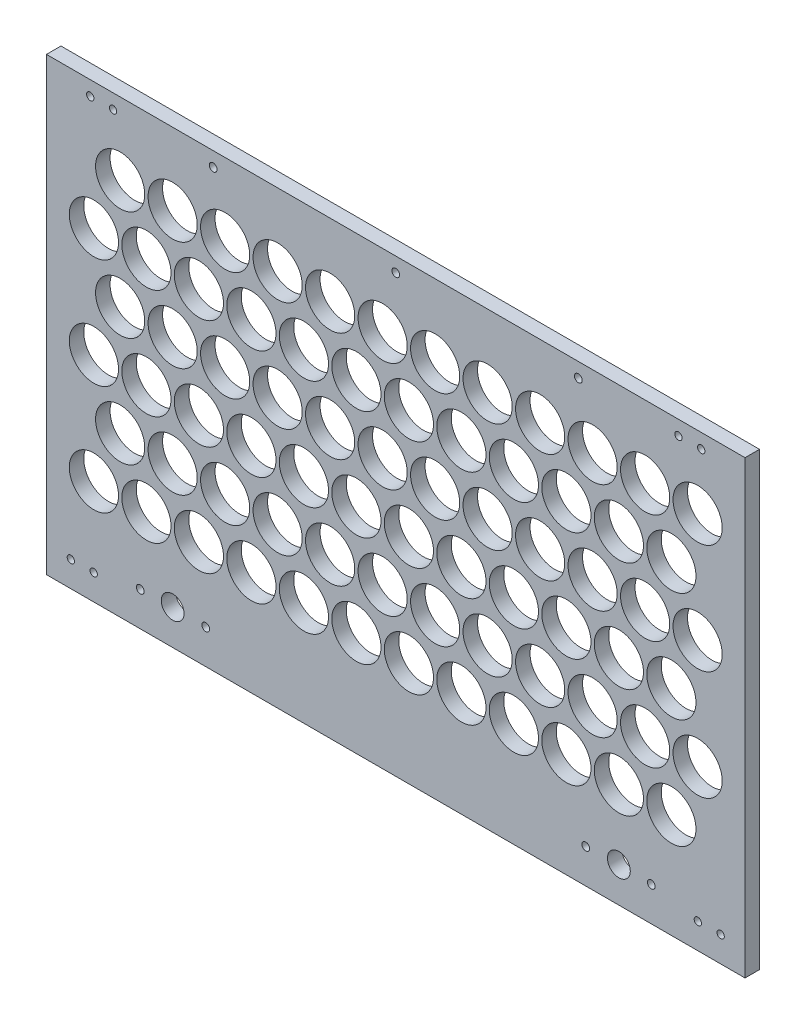
SolidWorks part; units mm, degrees
material "ABS"
ref_plane "X-Y Datum" through (0, 0, 0) normal (0, 0, 1) x (1, 0, 0)
ref_plane "X-Z Datum" through (0, 0, 0) normal (0, 1, 0) x (1, 0, 0)
ref_plane "Y-Z Datum" through (0, 0, 0) normal (1, 0, 0) x (0, 0, -1)
sketch "Sketch1" plane through (0, 0, 0) normal (0, 0, 1) x (1, 0, 0)
  line L1 (-143.025, 70.775) -> (143.025, 70.775)
  line L2 (-143.025, 70.775) -> (-143.025, -70.775)
  line L3 (-143.025, -70.775) -> (143.025, -70.775)
  line L4 (143.025, 70.775) -> (143.025, -70.775)
  line L5 (-143.025, 70.775) -> (143.025, -70.775) construction
  line L6 (-143.025, -70.775) -> (143.025, 70.775) construction
  line L13 (-153.025, -105.775) -> (153.025, -105.775)
  line L14 (-153.025, 91.65) -> (153.025, 91.65)
  line L15 (-153.025, 91.65) -> (-153.025, -105.775)
  line L16 (153.025, 91.65) -> (153.025, -105.775)
  line L17 (153.025, 70.775) -> (153.025, -70.775) construction
  line L18 (-143.025, 91.65) -> (143.025, 91.65) construction
  line L19 (-143.025, -105.775) -> (143.025, -105.775) construction
  line L20 (-153.025, 70.775) -> (-153.025, -70.775) construction
  line L21 (-132.25, -60) -> (-109.25, -60) construction
  circle A0 centre (-132.25, -60) radius 10.775
  circle A1 centre (-109.25, -60) radius 10.775 construction
  circle A2 centre (-120.75, -36) radius 10.775
  point P0 (0, 0)
  point P16 (-120.75, -60)
  dimension "D1" = 21.55
  dimension "D2" = 23
  dimension "D3" = 24
  dimension "D5" = 141.55
  dimension "D6" = 286.05
  dimension "D7" = 35
  dimension "D8" = 20.875
  dimension "D9" = 10
  dimension "D10" = 10
extrude "Boss-Extrude1" add sketch "Sketch1" along normal blind 6.35 contours A0 L3 L4 L1 L2 A2 | A2 | A0 | A0 L2 L3 | L1 L4 L3 L2 region at (2.4105, 0.9241, 0) region at (-140.6182, -68.3682, 0) region at (-132.25, -60, 0) region at (-149.383, -7.0625, 0) region at (-120.75, -36, 0)
sketch "Sketch3" plane through (0, 0, 6.35) normal (0, 0, 1) x (1, 0, 0)
  line L4 (143.025, 70.775) -> (-143.025, 70.775)
  line L5 (143.025, -70.775) -> (143.025, 70.775)
  line L6 (-143.025, -70.775) -> (143.025, -70.775)
  line L7 (-143.025, 70.775) -> (-143.025, -70.775)
  line L8 (143.025, 70.775) -> (-143.025, 70.775)
  line L9 (143.025, -70.775) -> (143.025, 70.775)
  line L10 (-143.025, -70.775) -> (143.025, -70.775)
  line L11 (-143.025, 70.775) -> (-143.025, -70.775)
  circle A1 centre (-120.75, -36) radius 10.775
  circle A2 centre (-120.75, -36) radius 10.775
  circle A3 centre (-132.25, -60) radius 10.775
  circle A4 centre (-132.25, -60) radius 10.775
  dimension "D1" = 0
  dimension "D2" = 0
  dimension "D3" = 0
extrude "Cut-Extrude1" cut sketch "Sketch3" against normal through all contours A4 region at (-132.25, -60, 6.35)
sketch "Sketch4" plane through (0, 0, 6.35) normal (0, 0, 1) x (1, 0, 0)
  line L4 (143.025, 70.775) -> (-143.025, 70.775)
  line L5 (143.025, -70.775) -> (143.025, 70.775)
  line L6 (-143.025, -70.775) -> (143.025, -70.775)
  line L7 (-143.025, 70.775) -> (-143.025, -70.775)
  line L8 (143.025, 70.775) -> (-143.025, 70.775)
  line L9 (143.025, -70.775) -> (143.025, 70.775)
  line L10 (-143.025, -70.775) -> (143.025, -70.775)
  line L11 (-143.025, 70.775) -> (-143.025, -70.775)
  circle A1 centre (-120.75, -36) radius 10.775
  circle A2 centre (-120.75, -36) radius 10.775
  circle A3 centre (-132.25, -60) radius 10.775
  circle A4 centre (-132.25, -60) radius 10.775
  dimension "D1" = 0
  dimension "D2" = 0
  dimension "D3" = 0
extrude "Cut-Extrude2" cut sketch "Sketch4" against normal through all contours A2 region at (-120.75, -36, 6.35)
pattern_linear "LPattern1" count 12 spacing 23 along (1, 0, 0) of "Cut-Extrude1", "Cut-Extrude2"
pattern_linear "LPattern2" count 3 spacing 48 along (0, 1, 0) of "LPattern1"
sketch "Sketch5" plane through (0, 0, 0) normal (0, 0, -1) x (-1, 0, 0)
  circle A0 centre (-97.75, -90.3965) radius 2 construction
  circle A1 centre (-97.75, -90.3965) radius 2 construction
  circle A2 centre (-97.75, -90.3965) radius 5
  dimension "D1" = 10
extrude "Cut-Extrude3" cut sketch "Sketch5" against normal through all
mirror "Mirror1" about plane through (0, 0, 0) normal (1, 0, 0) of "Cut-Extrude3"
sketch "Sketch7" plane through (0, 0, 0) normal (0, 0, -1) x (-1, 0, 0)
  line L0 (0, 3.4925) -> (0, -3.4925) construction
  point P0 (-111.94, -90.775)
  point P1 (-132.35, -94.6)
  point P3 (-142.35, -94.6)
  point P5 (-123.85, 85.3)
  point P7 (-133.85, 85.3)
  point P9 (-80, 85.3)
  point P11 (0, 85.3)
  point P13 (80, 85.3)
  point P15 (123.85, 85.3)
  point P17 (133.85, 85.3)
  point P19 (142.35, -94.6)
  point P21 (132.35, -94.6)
  point P23 (-83.25, -90.775)
  point P28 (83.25, -90.775)
  point P29 (111.94, -90.775)
hole_wizard "M3 Clearance Hole1" positions "Sketch8" profile "Sketch9" hole size "M3" standard "ANSI Metric" end condition through all
sketch "Sketch8" plane through (0, 0, 0) normal (0, 0, -1) x (-1, 0, 0)
  point P0 (-111.94, -90.775)
  point P3 (-80, 85.3)
  point P6 (0, 85.3)
  point P9 (80, 85.3)
  point P13 (-83.25, -90.775)
  point P17 (111.94, -90.775)
  point P20 (83.25, -90.775)
sketch "Sketch9" plane through (111.94, -90.775, 0) normal (1, 0, 0) x (0, 1, 0)
  line L0 (0, 0) -> (0, 6.35)
  line L1 (0, 6.35) -> (1.7, 6.35)
  line L2 (1.7, 6.35) -> (1.7, 0)
  line L5 (1.7, 0) -> (0, 0)
  line L11 (0, -6.35) -> (0, 107.95) construction
  dimension "Thru Hole Dia." = 3.4
  dimension "Thru Hole Depth" = 6.35
hole_wizard "M3 Clearance Hole2" positions "Sketch10" profile "Sketch11" hole size "M3" standard "ANSI Metric" end condition through all
sketch "Sketch10" plane through (0, 0, 0) normal (0, 0, -1) x (-1, 0, 0)
  point P0 (-142.35, -94.6)
  point P3 (-132.35, -94.6)
  point P6 (-133.85, 85.3)
  point P9 (-123.85, 85.3)
  point P12 (123.85, 85.3)
  point P15 (133.85, 85.3)
  point P18 (132.35, -94.6)
  point P21 (142.35, -94.6)
sketch "Sketch11" plane through (142.35, -94.6, 0) normal (1, 0, 0) x (0, 1, 0)
  line L0 (0, 0) -> (0, 6.35)
  line L1 (0, 6.35) -> (1.6, 6.35)
  line L2 (1.6, 6.35) -> (1.6, 0)
  line L5 (1.6, 0) -> (0, 0)
  line L11 (0, -6.35) -> (0, 107.95) construction
  dimension "Thru Hole Dia." = 3.2
  dimension "Thru Hole Depth" = 6.35
